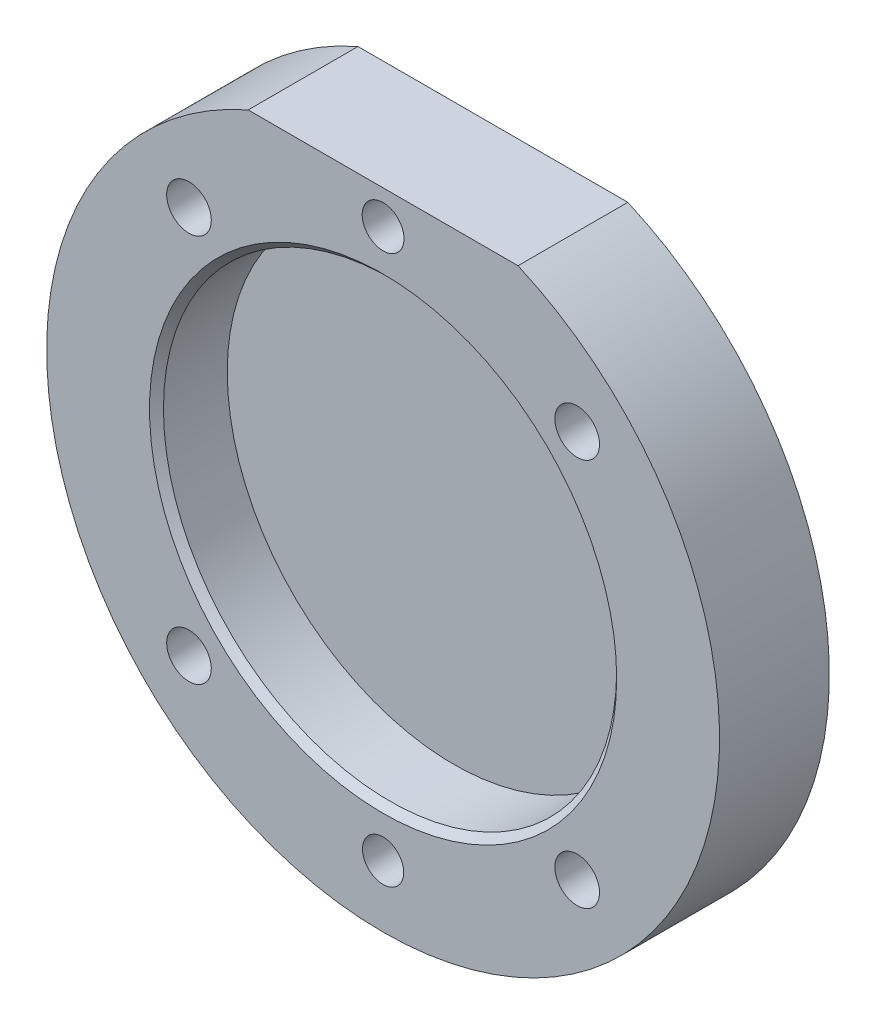
SolidWorks part; units mm, degrees
note: '?' marks a value the reader was unsure of.
ref_plane "Front" through (0, 0, 0) normal (0, 0, 1) x (1, 0, 0)
ref_plane "Top" through (0, 0, 0) normal (0, 1, 0) x (1, 0, 0)
ref_plane "Right" through (0, 0, 0) normal (1, 0, 0) x (0, 0, -1)
sketch "Sketch1" plane through (0, 0, 0) normal (0, 0, 1) x (1, 0, 0)
  line L0 (-9.8298, 22.4536) -> (9.8298, 22.4536)
  arc A0 (-9.8298, 22.4536) -> (9.8298, 22.4536) centre (0, 0) ccw
  dimension "D1" = 49.022
  dimension "D2" = 22.4536
extrude "Base-Extrude" add sketch "Sketch1" along normal blind 8.001
hole_wizard "Hole1" positions "Sketch3" profile "Sketch2" legacy end condition through all
sketch "Sketch3" plane through (0, 0, 8.001) normal (0, 0, 1) x (1, 0, 0)
  line L0 (0, 0) -> (0, 22.9534) construction
  point P0 (0, 20)
  dimension "D1" = 20
sketch "Sketch2" plane through (0, 20, 8.001) normal (1, 0, 0) x (0, -1, 0)
  line L0 (0, 0) -> (0, 8.001)
  line L1 (0, 8.001) -> (1.524, 8.001)
  line L2 (1.524, 8.001) -> (1.524, 0)
  line L3 (1.524, 0) -> (0, 0)
  line L4 (0, 110) -> (0, -10) construction
  dimension "Diameter" = 3.048
  dimension "Depth" = 8.001
hole_wizard "Hole2" positions "Sketch5" profile "Sketch4" legacy end condition through all
sketch "Sketch5" plane through (0, 0, 8.001) normal (0, 0, 1) x (1, 0, 0)
  line L0 (0, 0) -> (0, 20) construction
  line L1 (0, 0) -> (-20.0511, 20.0511) construction
  circle A0 centre (0, 0) radius 20 construction
  point P0 (-14.1421, 14.1421)
  dimension "D2" = 45
sketch "Sketch4" plane through (-14.1421, 14.1421, 8.001) normal (1, 0, 0) x (0, -1, 0)
  line L0 (0, 0) -> (0, 8.001)
  line L1 (0, 8.001) -> (1.6256, 8.001)
  line L2 (1.6256, 8.001) -> (1.6256, 0)
  line L3 (1.6256, 0) -> (0, 0)
  line L4 (0, 110) -> (0, -10) construction
  dimension "Diameter" = 3.2512
  dimension "Depth" = 8.001
ref_axis "Axis1" through (0, 0, 58.001) along (0, 0, -1)?
pattern_circular "CirPattern1" count 4 every 90 about axis through (0, 0, 0) along (0, 0, 1) of "Hole2"
hole_wizard "Hole3" positions "Sketch7" profile "Sketch6" legacy end condition through all
sketch "Sketch7" plane through (0, 0, 8.001) normal (0, 0, 1) x (1, 0, 0)
  line L0 (0, 0) -> (0, -25.8766) construction
  point P0 (0, -20.0025)
  dimension "D1" = 20.0025
sketch "Sketch6" plane through (0, -20.0025, 8.001) normal (1, 0, 0) x (0, -1, 0)
  line L0 (0, 0) -> (0, 8.001)
  line L1 (0, 8.001) -> (1.4999, 8.001)
  line L2 (1.4999, 8.001) -> (1.4999, 0)
  line L3 (1.4999, 0) -> (0, 0)
  line L4 (0, 110) -> (0, -10) construction
  dimension "Diameter" = 2.9997
  dimension "Depth" = 8.001
sketch "Sketch8" plane through (0, 0, 8.001) normal (0, 0, 1) x (1, 0, 0)
  circle A0 centre (0, 0) radius 16.51
  dimension "D1" = 33.02
extrude "Cut-Extrude1" cut sketch "Sketch8" against normal blind 5.1562
chamfer "Chamfer1" distance 0.508 angle 45 1 edges at (16.51, 0, 8.001)
